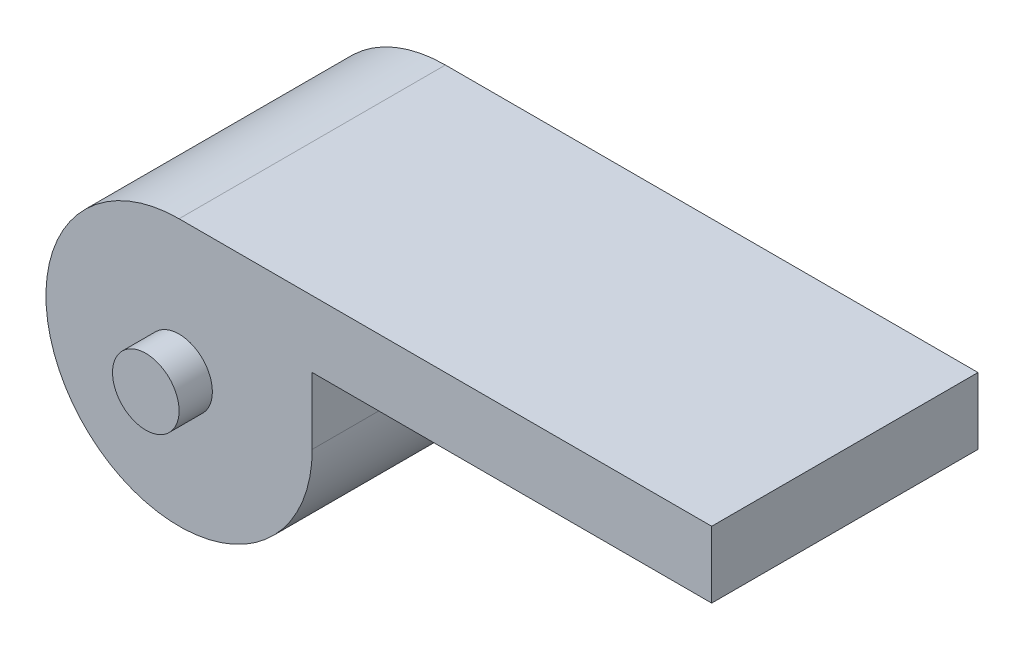
SolidWorks part; units mm, degrees
ref_plane "Front Plane" through (0, 0, 0) normal (0, 0, 1) x (1, 0, 0)
ref_plane "Top Plane" through (0, 0, 0) normal (0, 1, 0) x (1, 0, 0)
ref_plane "Right Plane" through (0, 0, 0) normal (1, 0, 0) x (0, 0, -1)
sketch "Sketch1" plane through (0, 0, 0) normal (0, 0, 1) x (1, 0, 0)
  line L0 (0, 6.35) -> (25.4, 6.35)
  line L1 (25.4, 6.35) -> (25.4, 3.175)
  line L2 (25.4, 3.175) -> (6.35, 3.175)
  line L3 (6.35, 3.175) -> (6.35, 0)
  circle A0 centre (0, 0) radius 6.35
  circle A1 centre (0, 0) radius 1.5875
  dimension "D1" = 3.175
  dimension "D2" = 12.7
  dimension "D3" = 25.4
  dimension "D4" = 3.175
extrude "Boss-Extrude1" add sketch "Sketch1" along normal blind 12.7 contours A0 A1 | A0 L3 L2 L1 L0 region at (14.5053, 4.7837, 0) region at (4.3631, 4.3631, 0)
extrude "Boss-Extrude2" add sketch "Sketch1<3>" along normal blind 14.2875 and the other way blind 1.5875 contours A1 region at (0, 0, 0)
sketch "Sketch1<3>" plane through (0, 0, 0) normal (0, 0, 1) x (1, 0, 0) same geometry as "Sketch1"
